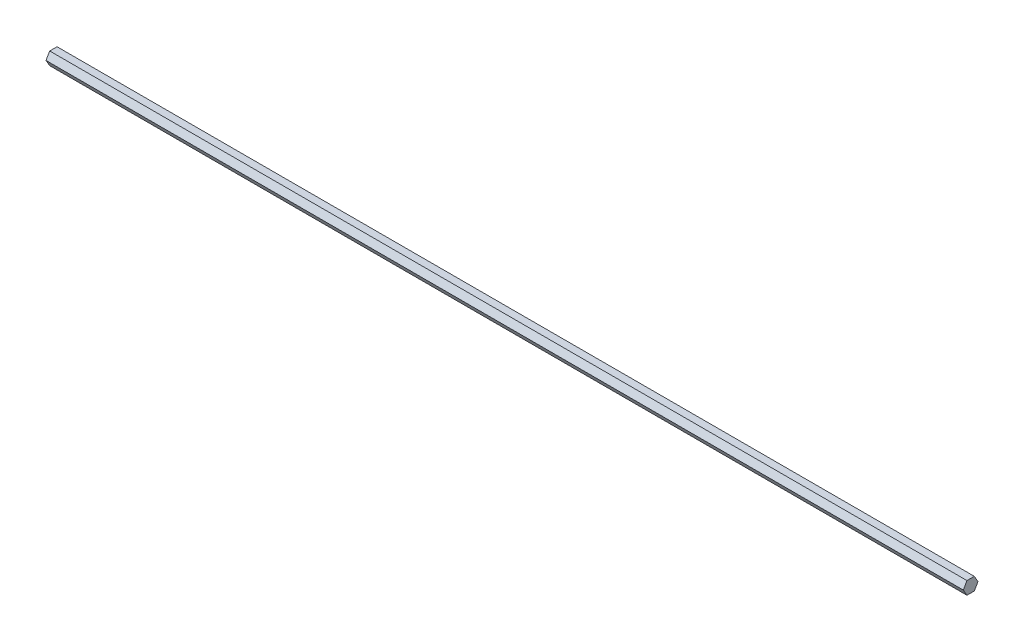
SolidWorks part; units mm, degrees
ref_plane "Front Plane" through (0, 0, 0) normal (0, 0, 1) x (1, 0, 0)
ref_plane "Top Plane" through (0, 0, 0) normal (0, 1, 0) x (1, 0, 0)
ref_plane "Right Plane" through (0, 0, 0) normal (1, 0, 0) x (0, 0, -1)
sketch "Sketch1" plane through (0, 0, 0) normal (1, 0, 0) x (0, 0, -1)
  line L1 (7.3323, 0) -> (3.6662, 6.35)
  line L2 (3.6662, 6.35) -> (-3.6662, 6.35)
  line L3 (-3.6662, 6.35) -> (-7.3323, 0)
  line L4 (-7.3323, 0) -> (-3.6662, -6.35)
  line L5 (-3.6662, -6.35) -> (3.6662, -6.35)
  line L6 (3.6662, -6.35) -> (7.3323, 0)
  circle A0 centre (0, 0) radius 6.35 construction
  dimension "D1" = 12.7
extrude "Boss-Extrude1" add sketch "Sketch1" along normal blind 914.4
ref_axis "Axis1" through (0, 0, 0) along (1, 0, 0)
